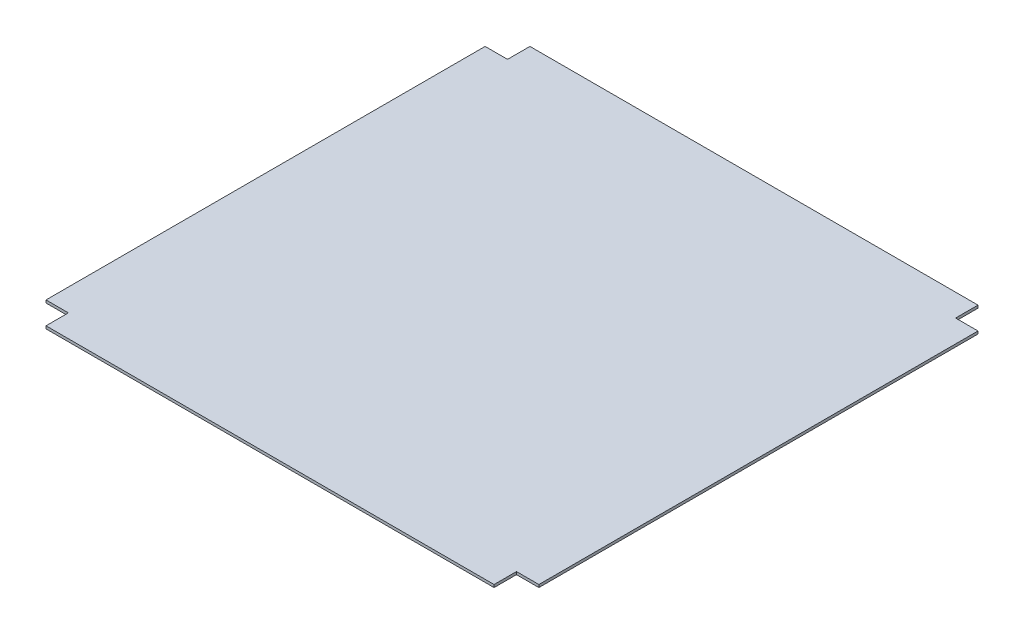
SolidWorks part; units mm, degrees
ref_plane "Front Plane" through (0, 0, 0) normal (0, 0, 1) x (1, 0, 0)
ref_plane "Top Plane" through (0, 0, 0) normal (0, 1, 0) x (1, 0, 0)
ref_plane "Right Plane" through (0, 0, 0) normal (1, 0, 0) x (0, 0, -1)
sketch "Sketch1" plane through (0, 0, 0) normal (0, 1, 0) x (1, 0, 0)
  line L0 (-1000, 0) -> (49000, 0) construction
  line L5 (250, 270) -> (250, 245)
  line L6 (250, 245) -> (275, 245)
  line L15 (-250, 270) -> (250, 270)
  line L25 (0, -1000) -> (0, 49000) construction
  line L26 (275, 245) -> (275, -245)
  line L27 (-275, 245) -> (-275, -245)
  line L28 (-250, 245) -> (-275, 245)
  line L29 (-250, 270) -> (-250, 245)
  line L30 (-250, -270) -> (-250, -245)
  line L31 (-250, -245) -> (-275, -245)
  line L32 (-250, -270) -> (250, -270)
  line L33 (250, -245) -> (275, -245)
  line L34 (250, -270) -> (250, -245)
  point P0 (0, 0)
  point P7 (0, 270)
  point P13 (-275, 0)
  point P15 (275, 0)
  point P19 (0, -270)
  dimension "D1" = 270
  dimension "D2" = 25
  dimension "D3" = 250
base flange "Base-Flange1" sketch "Sketch1" thickness 3 reverse thickness direction no parameters "D1"=0.7366
sketch "Bend-Lines1" [suppressed] plane through (0, 0, 0) normal (0, 1, 0) x (1, 0, 0)
sketch "Bounding-Box1" [suppressed] plane through (0, 0, 0) normal (0, 1, 0) x (1, 0, 0)
sheet metal parameters "Sheet-Metal1" thickness 3 parameters "D1"=0.7366
flat pattern "Flat-Pattern1" [suppressed]
sketch "Bend-Lines2" plane through (0, 0, 0) normal (0, 1, 0) x (1, 0, 0)
sketch3d "Bounding-Box2" [suppressed]
  line L0 (275, 270, 0) -> (-275, 270, 0) construction
  line L1 (275, -270, 0) -> (-275, -270, 0) construction
  line L2 (275, 270, 0) -> (275, -270, 0) construction
  line L3 (-275, 270, 0) -> (-275, -270, 0) construction
